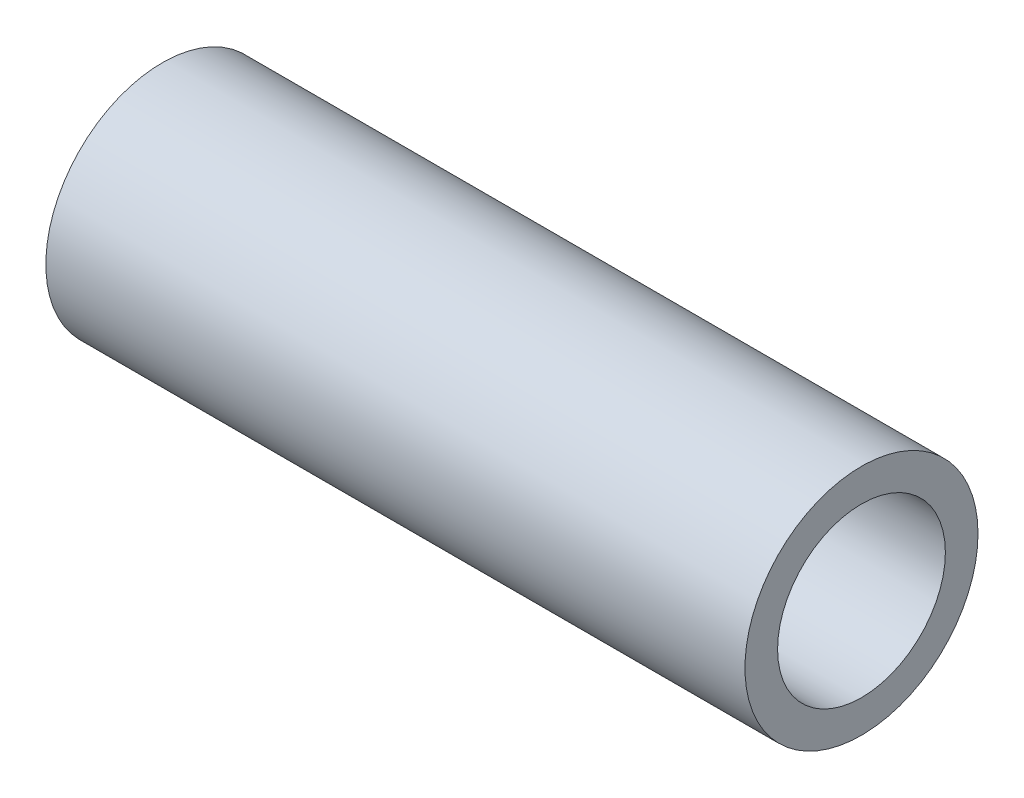
SolidWorks part; units mm, degrees
ref_plane "Front" through (0, 0, 0) normal (0, 0, 1) x (1, 0, 0)
ref_plane "Top" through (0, 0, 0) normal (0, 1, 0) x (1, 0, 0)
ref_plane "Right" through (0, 0, 0) normal (1, 0, 0) x (0, 0, -1)
sketch "Sketch1" plane through (0, 0, 0) normal (1, 0, 0) x (0, 0, -1)
  circle A0 centre (0, 0) radius 5
  dimension "d" = 10
extrude "Base-Extrude" add sketch "Sketch1" along normal blind 30
sketch "Sketch2" plane through (0, 0, 0) normal (0, 0, 1) x (1, 0, 0)
  line L0 (15, 7.0065) -> (15, -7.6583) construction
  line L2 (-23.677, 0) -> (34.1961, 0) construction
  line L3 (30, 0) -> (30, 3.6)
  line L4 (30, -5) -> (30, 5) construction
  line L5 (30, 3.6) -> (23.35, 3.6)
  line L6 (23.35, 3.6) -> (20.7344, 0)
  line L7 (20.7344, 0) -> (30, 0)
  line L8 (9.2656, 0) -> (0, 0)
  line L9 (6.65, 3.6) -> (9.2656, 0)
  line L10 (0, 3.6) -> (6.65, 3.6)
  line L11 (0, 0) -> (0, 3.6)
  line L12 (0, 5) -> (0, -5) construction
  dimension "dt" = 7.2
  dimension "t" = 6.65
  dimension "D3" = 54
revolve "Cut-Revolve1" cut sketch "Sketch2" angle 360 about L2
